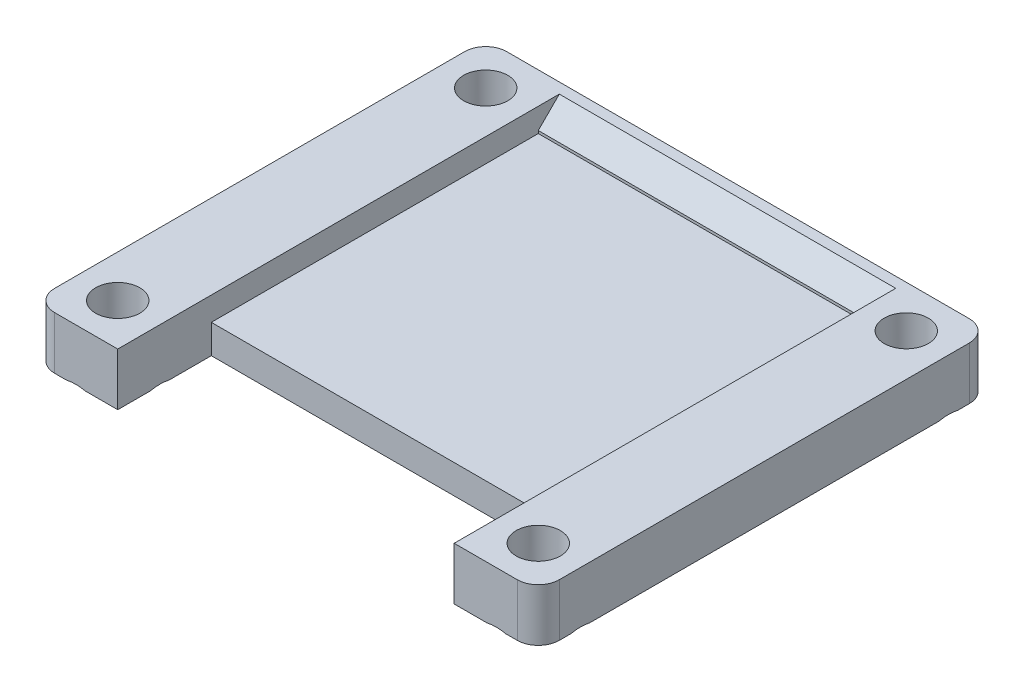
SolidWorks part; units mm, degrees
ref_plane "Спереди" through (0, 0, 0) normal (0, 0, 1) x (1, 0, 0)
ref_plane "Сверху" through (0, 0, 0) normal (0, 1, 0) x (1, 0, 0)
ref_plane "Справа" through (0, 0, 0) normal (1, 0, 0) x (0, 0, -1)
sketch "Эскиз1" plane through (0, 0, 0) normal (0, 1, 0) x (1, 0, 0)
  line L0 (-24, 43) -> (-24, -5) construction
  line L1 (-48, 43) -> (0, 43)
  line L2 (-48, 43) -> (-48, 0)
  line L3 (-48, 0) -> (0, 0)
  line L4 (0, 43) -> (0, 0)
  line L5 (-48, 21.5) -> (0, 21.5) construction
  point P6 (-24, 43)
  dimension "D1" = 43
  dimension "D2" = 48
extrude "Бобышка-Вытянуть1" add sketch "Эскиз1" against normal blind 5
sketch "Эскиз2" plane through (0, 0, 0) normal (0, 1, 0) x (1, 0, 0)
  line L0 (-48, 43) -> (-48, 0) construction
  line L1 (-40, 40) -> (-8, 40)
  line L2 (-40, 40) -> (-40, 0)
  line L3 (-40, 0) -> (-8, 0)
  line L4 (-8, 40) -> (-8, 0)
  line L5 (0, 0) -> (0, 43) construction
  line L7 (0, 43) -> (-48, 43) construction
  line L8 (-48, 0) -> (0, 0) construction
  line L9 (-48, 21.5) -> (0, 21.5) construction
  line L10 (-24, 43) -> (-24, -0.4774) construction
  point P16 (-24, 0)
  dimension "D1" = 8
  dimension "D2" = 8
  dimension "D4" = 3
extrude "Вырез-Вытянуть1" cut sketch "Эскиз2" against normal blind 2.25
sketch "Эскиз3" plane through (0, 0, 0) normal (0, 1, 0) x (1, 0, 0)
  line L0 (-48, 21.5) -> (0, 21.5) construction
  line L1 (-48, 43) -> (-48, 0) construction
  line L2 (0, 0) -> (0, 43) construction
  line L3 (-24, 43) -> (-24, 0) construction
  line L4 (0, 43) -> (-48, 43) construction
  line L5 (-40, 0) -> (-8, 0) construction
  circle A0 centre (-44, 39) radius 2.1
  circle A1 centre (-4, 39) radius 2.1
  circle A2 centre (-4, 4) radius 2.1
  circle A3 centre (-44, 4) radius 2.1
  dimension "D1" = 4.2
  dimension "D2" = 4
  dimension "D3" = 4
extrude "Вырез-Вытянуть2" cut sketch "Эскиз3" against normal through all
chamfer "Фаска1" distance 2 angle 45 4 edges at (-4, -5, -1.9) (-44, -5, -6.1) (-44, -5, -36.9) (-4, -5, -41.1)
fillet "Скругление1" radius 2 4 edges at (-48, -2.5, 0) (0, -2.5, 0) (0, -2.5, -43) (-48, -2.5, -43)
chamfer "Фаска2" distance 2 angle 45 1 edges at (-24, 0, -40)
sketch "Эскиз4" plane through (0, -2.25, 0) normal (0, 1, 0) x (1, 0, 0)
  line L0 (-8, 0) -> (-8, 42) construction
  line L1 (-40, 0) -> (-8, 0)
  line L2 (-40, 0) -> (-40, 8.9)
  line L3 (-40, 8.9) -> (-8, 8.9)
  line L4 (-8, 0) -> (-8, 8.9)
  circle A5 centre (-4, 39) radius 2.1 construction
  dimension "D1" = 28
extrude "Вырез-Вытянуть3" cut sketch "Эскиз4" against normal through all
